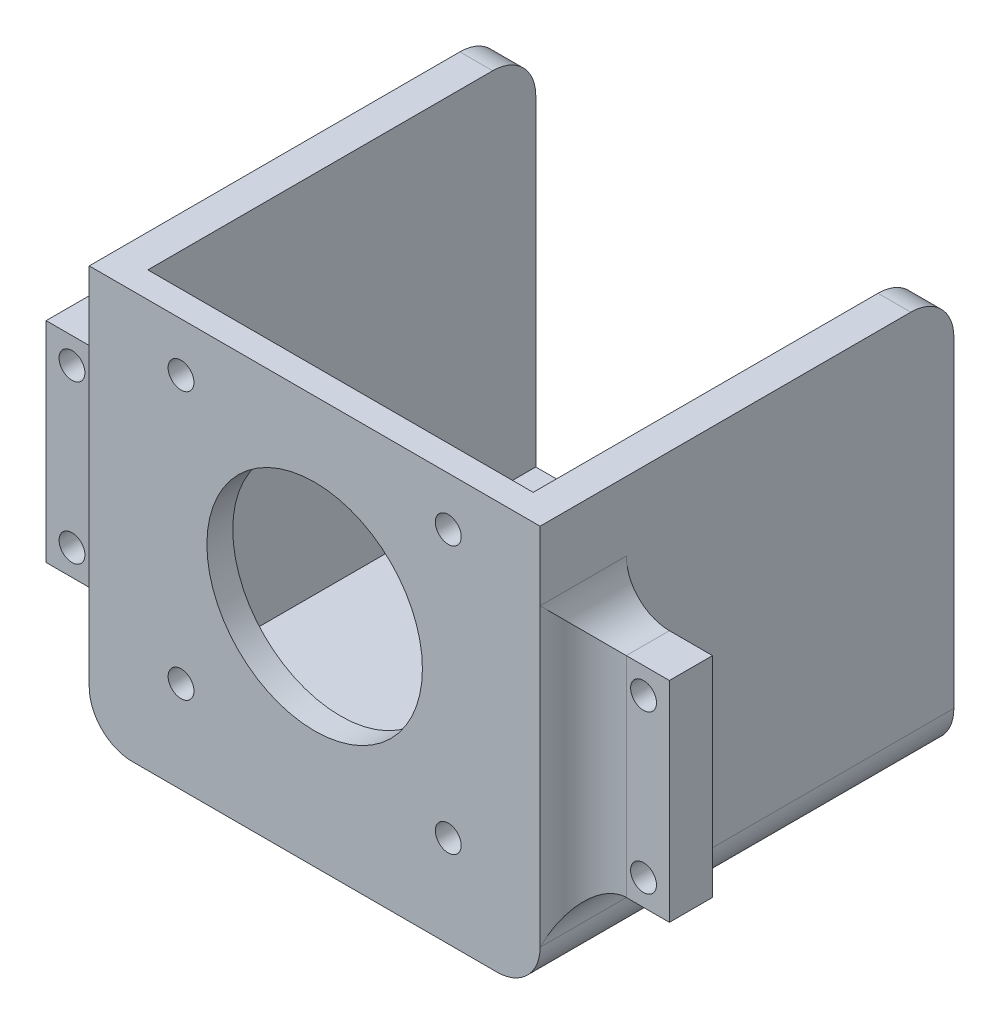
SolidWorks part; units mm, degrees
ref_plane "前视基准面" through (0, 0, 0) normal (0, 0, 1) x (1, 0, 0)
ref_plane "上视基准面" through (0, 0, 0) normal (0, 1, 0) x (1, 0, 0)
ref_plane "右视基准面" through (0, 0, 0) normal (1, 0, 0) x (0, 0, -1)
other "Configuration Table"
sketch "草图1" plane through (0, 0, 0) normal (0, 0, 1) x (1, 0, 0)
  line L1 (21.15, -21.15) -> (-21.15, -21.15)
  line L2 (21.15, -21.15) -> (21.15, 21.15)
  line L3 (21.15, 21.15) -> (-21.15, 21.15)
  line L4 (-21.15, -21.15) -> (-21.15, 21.15)
  line L5 (21.15, -21.15) -> (-21.15, 21.15) construction
  line L6 (21.15, 21.15) -> (-21.15, -21.15) construction
  point P0 (0, 0)
  dimension "D1" = 42.3
  dimension "D2" = 42.3
extrude "凸台-拉伸1" add sketch "草图1" along normal blind 3
sketch "草图2" plane through (0, 0, 3) normal (0, 0, 1) x (1, 0, 0)
  line L1 (15.5, -15.5) -> (-15.5, -15.5) construction
  line L2 (15.5, -15.5) -> (15.5, 15.5) construction
  line L3 (15.5, 15.5) -> (-15.5, 15.5) construction
  line L4 (-15.5, -15.5) -> (-15.5, 15.5) construction
  line L5 (15.5, -15.5) -> (-15.5, 15.5) construction
  line L6 (15.5, 15.5) -> (-15.5, -15.5) construction
  circle A0 centre (-15.5, 15.5) radius 1.5
  circle A1 centre (15.5, 15.5) radius 1.5
  circle A2 centre (15.5, -15.5) radius 1.5
  circle A3 centre (-15.5, -15.5) radius 1.5
  point P0 (0, 0)
  point P16 (0, 0)
  dimension "D3" = 4
  dimension "D1" = 31
  dimension "D2" = 31
extrude "切除-拉伸1" cut sketch "草图2" against normal blind 3
sketch "草图3" plane through (0, 0, 3) normal (0, 0, 1) x (1, 0, 0)
  circle A0 centre (0, 0) radius 12.5
  dimension "D1" = 25
extrude "切除-拉伸2" cut sketch "草图3" against normal blind 3
sketch "草图4" plane through (0, 0, 3) normal (0, 0, 1) x (1, 0, 0)
  line L0 (21.15, 21.15) -> (-21.15, 21.15) construction
  line L1 (26.15, -26.15) -> (-26.15, -26.15)
  line L2 (26.15, -26.15) -> (26.15, 26.15)
  line L3 (26.15, 26.15) -> (-26.15, 26.15)
  line L4 (-26.15, -26.15) -> (-26.15, 26.15)
  line L5 (26.15, -26.15) -> (-26.15, 26.15) construction
  line L6 (26.15, 26.15) -> (-26.15, -26.15) construction
  line L7 (-26.15, 21.15) -> (26.15, 21.15)
  line L8 (21.15, -21.15) -> (-21.15, -21.15)
  line L9 (21.15, -21.15) -> (21.15, 21.15)
  line L10 (21.15, 21.15) -> (-21.15, 21.15)
  line L11 (-21.15, -21.15) -> (-21.15, 21.15)
  line L12 (21.15, -21.15) -> (-21.15, 21.15) construction
  line L13 (21.15, 21.15) -> (-21.15, -21.15) construction
  point P0 (0, 0)
  point P8 (0, 0)
  line M14 (-21.15, 21.15) -> (-21.15, -21.15)
  line M15 (-21.15, -21.15) -> (21.15, -21.15)
  line M16 (21.15, -21.15) -> (21.15, 21.15)
  dimension "D1" = 5
extrude "凸台-拉伸2" add sketch "草图4" against normal blind 48 contours L7 L4 L1 L2 M16 M15 M14 region at (0, -25.4448, 3)
sketch "草图5" plane through (-26.15, 0, 0) normal (-1, 0, 0) x (0, 0, 1)
  line L0 (-45, -26.15) -> (3, -26.15) construction
  line L1 (-7, -26.15) -> (-2, -26.15)
  line L2 (-7, -26.15) -> (-7, 21.15)
  line L3 (-7, 21.15) -> (-2, 21.15)
  line L4 (-2, -26.15) -> (-2, 21.15)
  line L5 (3, -26.15) -> (3, 21.15) construction
  line L6 (-45, 21.15) -> (3, 21.15) construction
  dimension "D1" = 5
  dimension "D2" = 5
extrude "凸台-拉伸3" add sketch "草图5" along normal blind 10
sketch "草图6" plane through (26.15, 0, 0) normal (1, 0, 0) x (0, 0, -1)
  line L0 (45, 21.15) -> (-3, 21.15) construction
  line L1 (2, -26.15) -> (7, -26.15)
  line L2 (2, -26.15) -> (2, 21.15)
  line L3 (2, 21.15) -> (7, 21.15)
  line L4 (7, -26.15) -> (7, 21.15)
  line L5 (-3, -26.15) -> (-3, 21.15) construction
  line L6 (45, -26.15) -> (-3, -26.15) construction
  dimension "D1" = 5
  dimension "D2" = 5
extrude "凸台-拉伸4" add sketch "草图6" along normal blind 10
sketch "草图7" plane through (0, 0, 3) normal (0, 0, 1) x (1, 0, 0)
  line L0 (0, -26.15) -> (0, 21.15) construction
  line L1 (26.15, -26.15) -> (-26.15, -26.15) construction
  line L2 (26.15, 21.15) -> (-26.15, 21.15) construction
  line L3 (-36.15, -26.15) -> (-36.15, 21.15) construction
  circle A0 centre (-33.15, -13.15) radius 1.5
  circle A1 centre (-33.15, 5.15) radius 1.5
  circle A2 centre (33.15, -13.15) radius 1.5
  circle A3 centre (33.15, 5.15) radius 1.5
  dimension "D1" = 16
  dimension "D2" = 3
  dimension "D3" = 13
extrude "切除-拉伸3" cut sketch "草图7" against normal blind 10
sketch "草图8" plane through (0, 21.15, 0) normal (0, 1, 0) x (1, 0, 0)
  line L0 (-22.35, 45) -> (-22.35, 0)
  line L1 (-26.15, 45) -> (-21.15, 45) construction
  line L2 (-22.35, 0) -> (22.35, 0)
  line L3 (22.35, 0) -> (22.35, 45)
  line L4 (21.15, 45) -> (26.15, 45) construction
  line L5 (22.35, 45) -> (-22.35, 45)
  line L6 (-21.15, 45) -> (-21.15, 0) construction
  line L7 (21.15, 45) -> (21.15, 0) construction
  dimension "D1" = 1.2
  dimension "D2" = 1.2
extrude "切除-拉伸4" cut sketch "草图8" against normal up to surface (42.3 mm away)
sketch "草图10" plane through (0, 0, -2) normal (0, 0, 1) x (1, 0, 0)
  line L0 (-26.15, -26.15) -> (-26.15, 21.15) construction
  line L1 (-36.15, 21.15) -> (-26.15, 21.15)
  line L2 (-36.15, 21.15) -> (-36.15, 8.15)
  line L3 (-36.15, 8.15) -> (-26.15, 8.15)
  line L4 (-26.15, 21.15) -> (-26.15, 8.15)
  line L5 (26.15, 21.15) -> (26.15, -26.15) construction
  line L6 (36.15, 21.15) -> (26.15, 21.15)
  line L7 (36.15, 21.15) -> (36.15, 8.15)
  line L8 (36.15, 8.15) -> (26.15, 8.15)
  line L9 (26.15, 21.15) -> (26.15, 8.15)
  line L11 (-36.15, -26.15) -> (-26.15, -26.15)
  line L12 (-36.15, -26.15) -> (-36.15, -16.15)
  line L13 (-36.15, -16.15) -> (-26.15, -16.15)
  line L14 (-26.15, -26.15) -> (-26.15, -16.15)
  line L15 (36.15, -26.15) -> (26.15, -26.15)
  line L16 (36.15, -26.15) -> (36.15, -16.15)
  line L17 (36.15, -16.15) -> (26.15, -16.15)
  line L18 (26.15, -26.15) -> (26.15, -16.15)
  dimension "D1" = 13
  dimension "D2" = 13
  dimension "D3" = 10
  dimension "D4" = 10
extrude "切除-拉伸5" cut sketch "草图10" against normal blind 10
fillet "圆角1" radius 5 1 edges at (-26.15, -4, -2)
fillet "圆角2" radius 5 1 edges at (26.15, -4, -2)
fillet "圆角3" radius 5 1 edges at (-26.15, 8.15, -2)
fillet "圆角4" radius 5 1 edges at (-26.15, -16.15, -2)
fillet "圆角5" radius 5 2 edges at (26.15, -16.15, -2) (26.15, 8.15, -2)
fillet "圆角6" radius 5 2 edges at (-24.25, 21.15, -45) (24.25, 21.15, -45)
fillet "圆角7" radius 5 2 edges at (26.15, -26.15, -21) (-26.15, -26.15, -21)
